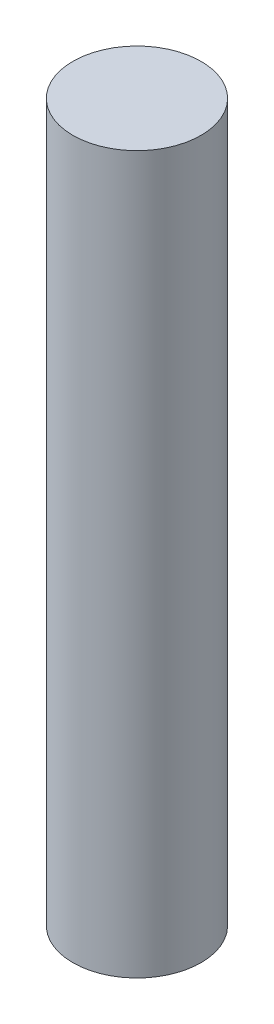
SolidWorks part; units mm, degrees
ref_plane "Front Plane" through (0, 0, 0) normal (0, 0, 1) x (1, 0, 0)
ref_plane "Top Plane" through (0, 0, 0) normal (0, 1, 0) x (1, 0, 0)
ref_plane "Right Plane" through (0, 0, 0) normal (1, 0, 0) x (0, 0, -1)
sketch "Sketch1" plane through (0, 0, 0) normal (0, 1, 0) x (1, 0, 0)
  circle A0 centre (0, 0) radius 3.175
  dimension "D1" = 6.35
sketch "Sketch2" plane through (0, 0, 0) normal (1, 0, 0) x (0, 0, -1)
  line L0 (0, 0) -> (0, 35.4842)
  circle A0 centre (0, 0) radius 35.4842 construction
extrude "Boss-Extrude1" add sketch "Sketch1" along normal up to vertex (35.4842 mm away) contours A0 up to point (0, 35.4842, 0)
